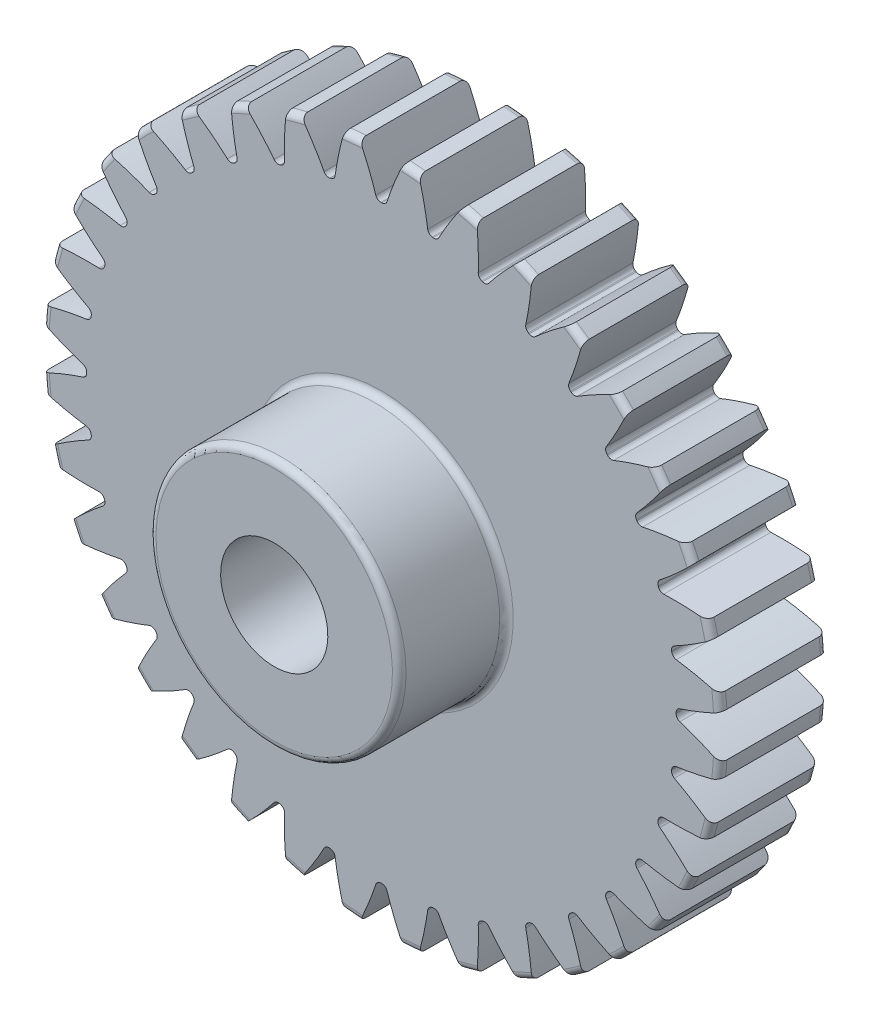
SolidWorks part; units mm, degrees
material "Delrin 2700 NC010, Low Viscosity Acetal Copolymer (SS)"
ref_plane "Front Plane" through (0, 0, 0) normal (0, 0, 1) x (1, 0, 0)
ref_plane "Top Plane" through (0, 0, 0) normal (0, 1, 0) x (1, 0, 0)
ref_plane "Right Plane" through (0, 0, 0) normal (1, 0, 0) x (0, 0, -1)
sketch "Sketch1" plane through (0, 0, 0) normal (0, 0, 1) x (1, 0, 0)
  line L0 (-457.2, 0) -> (457.2, 0) construction
  circle A0 centre (0, 0) radius 19 construction
  circle A1 centre (0, 0) radius 18 construction
  circle A2 centre (0, 0) radius 16.5 construction
  circle A3 centre (0, 0) radius 7 construction
  circle A4 centre (0, 0) radius 3 construction
  dimension "D2" = 1
  dimension "D3" = 2.5
  dimension "D1" = 2.5
sketch "Sketch2" plane through (0, 0, 0) normal (1, 0, 0) x (0, 0, -1)
  line L0 (0, 0) -> (-6, 0) construction
  line L1 (-6, 0) -> (-12, 0) construction
  dimension "Overall Width" = 12
  dimension "Face Width" = 6
sketch "Sketch4" plane through (0, 0, 0) normal (1, 0, 0) x (0, 0, -1)
  line L0 (-12, 3) -> (-12, 7)
  line L1 (-12, 7) -> (-6, 7)
  line L2 (-6, 7) -> (-6, 19)
  line L3 (-6, 19) -> (0, 19)
  line L4 (0, 19) -> (0, 3)
  line L5 (-6, 7) -> (-6, 0) construction
  line L6 (0, 19) -> (0, -19) construction
  line L7 (-6, 7) -> (0, 7) construction
  line L12 (-12, 3) -> (0, 3)
revolve "Revolve1" add sketch "Sketch4" angle 360 about L1
fillet "Fillet2" radius 0.38 4 edges at (0, 7, 12) (0, 7, 6) (0, 19, 6) (0, 19, 0)
sketch "Sketch7" plane through (0, 0, 6) normal (0, 0, 1) x (1, 0, 0)
  line L0 (0, 0) -> (0, 19) construction
  line L1 (0.7851, 17.9829) -> (1.191, 18.9626) construction
  line L3 (1.656, 18.9277) -> (1.5688, 17.9315) construction
  line L4 (1.5688, 17.9315) -> (1.4381, 16.4372) construction
  line L5 (0, 0) -> (1.4381, 16.4372) construction
  line L6 (0.7851, 17.9829) -> (0, 0) construction
  line L7 (0.7851, 17.9829) -> (0.8288, 18.9819) construction
  line L8 (0.7851, 17.9829) -> (0, 0) construction
  circle A0 centre (0, 0) radius 19 construction
  arc A1 (-0.0266, 16.5) -> (0.0266, 16.5) centre (0, 0) cw
  circle A2 centre (0, 0) radius 16.5 construction
  arc A3 (-0.7851, 17.9829) -> (0.7851, 17.9829) centre (0, 0) cw construction
  circle A4 centre (0, 0) radius 18 construction
  arc A5 (2.0864, 18.8851) -> (1.2246, 18.9605) centre (0, 0) ccw construction
  arc A6 (0.7851, 17.9829) -> (2.3495, 17.846) centre (0, 0) cw construction
  arc A7 (-1.2246, 18.9605) -> (1.2246, 18.9605) centre (0, 0) cw
  arc A8 (0.3122, 16.7065) -> (1.2246, 18.9605) centre (17.415, 11.0946) cw
  arc A9 (-0.3122, 16.7065) -> (-1.2246, 18.9605) centre (-17.415, 11.0946) ccw
  arc A10 (-0.0266, 16.5) -> (-0.3122, 16.7065) centre (-0.0271, 16.8) cw
  arc A11 (0.0266, 16.5) -> (0.3122, 16.7065) centre (0.0271, 16.8) ccw
  point P26 (-0.2452, 16.4982)
  point P29 (0.2452, 16.4982)
  dimension "D4" = 0.3
  dimension "D5" = 18
  dimension "D3" = 20
  dimension "D1" = 3.1416
  dimension "D2" = 1.5708
extrude "Cut-Extrude2" cut sketch "Sketch7" against normal through all
pattern_circular "CirPattern1" count 36 over 360 about axis through (0, 0, 12) along (0, 0, -1) of "Cut-Extrude2"
equation "\"D1@Sketch1\"=2.5*(\"Pitch Dia.@Sketch1\"/\"Number of Teeth@Sketch1\")"
equation "\"D1@CirPattern1\"=\"Number of Teeth@Sketch1\""
equation "\"D1@Fillet2\"=\"OD@Sketch1\"*.01"
equation "\"D1@Sketch7\"=3.14159*(\"Pitch Dia.@Sketch1\"/\"Number of Teeth@Sketch1\")"
equation "\"D2@Sketch7\"=\"D1@Sketch7\"/2"
equation "\"D4@Sketch7\"=\"D1@Sketch7\"*.0955"
equation "\"D5@Sketch7\"=\"Pitch Dia.@Sketch1\"/2"
